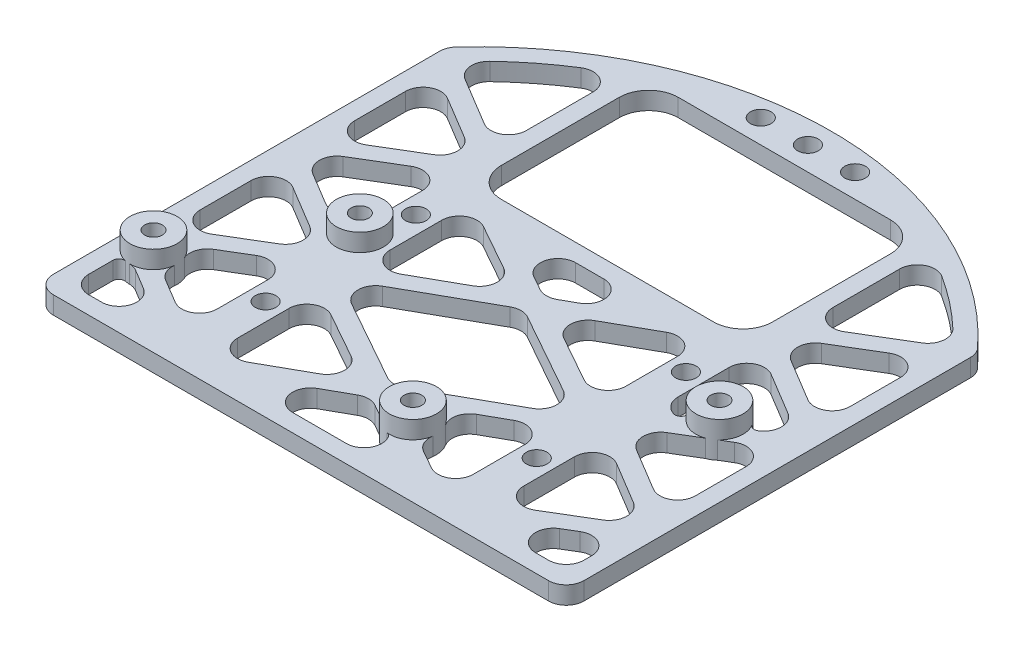
SolidWorks part; units mm, degrees
ref_plane "Front Plane" through (0, 0, 0) normal (0, 0, 1) x (1, 0, 0)
ref_plane "Top Plane" through (0, 0, 0) normal (0, 1, 0) x (1, 0, 0)
ref_plane "Right Plane" through (0, 0, 0) normal (1, 0, 0) x (0, 0, -1)
sketch "Sketch1" plane through (0, 0, 0) normal (0, 1, 0) x (1, 0, 0)
  line L0 (-45, -30) -> (45, -30)
  line L1 (45, -30) -> (45, 39.6863)
  line L2 (-45, -30) -> (-45, 39.6863)
  line L3 (0, 0) -> (0, 50000) construction
  arc A0 (-45, 39.6863) -> (45, 39.6863) centre (0, 0) cw
  dimension "D3" = 60
  dimension "D1" = 90
  dimension "D2" = 30
extrude "Boss-Extrude1" add sketch "Sketch1" along normal blind 3
sketch "Sketch2" plane through (0, 3, 0) normal (0, 1, 0) x (1, 0, 0)
  line L0 (0, 0) -> (0, 50000) construction
  line L1 (-45, -30) -> (45, -30) construction
  line L2 (-21.0323, 60) -> (49978.9677, 60) construction
  line L3 (-23, 52) -> (23, 52)
  line L4 (-23, 52) -> (-23, 22)
  line L5 (-23, 22) -> (23, 22)
  line L6 (23, 52) -> (23, 22)
  arc A0 (45, 39.6863) -> (-45, 39.6863) centre (0, 0) ccw construction
  point P4 (0, -30)
  dimension "D1" = 46
  dimension "D2" = 30
  dimension "D3" = 8
extrude "Cut-Extrude1" cut sketch "Sketch2" against normal through all
sketch "Sketch4" plane through (0, 3, 0) normal (0, 1, 0) x (1, 0, 0)
  circle A0 centre (23, -13) radius 1.75
  circle A1 centre (23, 12.2995) radius 1.75
  circle A2 centre (-23, 12.5) radius 1.75
  circle A3 centre (-23, -13) radius 1.75
  dimension "D1" = 3.5
extrude "Cut-Extrude3" cut sketch "Sketch4" against normal through all
sketch "Sketch8" plane through (0, 3, 0) normal (0, 1, 0) x (1, 0, 0)
  line L0 (0, 0) -> (0, 50000) construction
  line L1 (-4.2053, 56) -> (49995.7947, 56) construction
  circle A0 centre (0, 56) radius 1.75
  circle A1 centre (0, 56) radius 1.75 construction
  circle A2 centre (-8, 56) radius 1.75
  circle A3 centre (8, 56) radius 1.75
  dimension "D1" = 16
extrude "Cut-Extrude6" cut sketch "Sketch8" against normal through all
sketch "Sketch9" plane through (0, 3, 0) normal (0, 1, 0) x (1, 0, 0)
  line L0 (-42, 35.0364) -> (-42, 15.8207)
  line L1 (-42, 38.5357) -> (-26, 28.9279)
  line L2 (-42, -27) -> (-26, -27)
  line L3 (-42, 35.0364) -> (-26, 25.4286)
  line L4 (-13.8683, 19) -> (13.8683, 19)
  line L5 (-45, 39.6863) -> (-45, -30) construction
  line L6 (13.8683, 19) -> (0, 11.2199)
  line L7 (0, 11.2199) -> (-13.8683, 19)
  line L8 (-26, 25.4286) -> (-42, 15.8207)
  line L9 (-20, 19) -> (-3.0658, 9.5)
  line L10 (-3.0658, 9.5) -> (-20, 0)
  line L11 (20, 19) -> (3.0658, 9.5)
  line L12 (3.0658, 9.5) -> (20, 0)
  line L13 (-20, -3.4398) -> (0, 7.7801)
  line L14 (0, 7.7801) -> (20, -3.4398)
  line L15 (-20, -3.4398) -> (0, -14.6597)
  line L16 (0, -14.6597) -> (20, -3.4398)
  line L17 (20, -6.8797) -> (3.0658, -16.3797) construction
  line L18 (3.0658, -16.3797) -> (20, -25.8797) construction
  line L19 (20, -25.8797) -> (20, -6.8797)
  line L20 (0, 0) -> (0, -50000) construction
  line L21 (-20, -6.8797) -> (-20, -25.8797)
  line L22 (-20, 0) -> (-20, 19)
  line L23 (-26, 21.9292) -> (-42, 12.3214)
  line L24 (-42, 12.3214) -> (-26, 2.7136)
  line L25 (42, -27) -> (26, -27)
  line L26 (-42, 8.8221) -> (-26, -0.7857)
  line L27 (-26, -0.7857) -> (-42, -10.3935)
  line L28 (-26, -4.285) -> (-42, -13.8929)
  line L29 (-26, 50.7247) -> (-26, 28.9279)
  line L30 (-42, -13.8929) -> (-26, -23.5007)
  line L31 (-20, -25.8797) -> (-3.0658, -16.3797)
  line L32 (26, -23.5007) -> (26, -4.285)
  line L33 (42, 35.0364) -> (42, 15.8207)
  line L34 (-42, -17.3922) -> (-26, -27)
  line L35 (-39.5573, -13.8929) -> (49960.4427, -13.8929) construction
  line L36 (-28.2048, -0.7857) -> (-50028.2048, -0.7857) construction
  line L37 (-45, -30) -> (45, -30) construction
  line L38 (-39.4376, 12.3214) -> (49960.5624, 12.3214) construction
  line L39 (0, 0) -> (50000, 0) construction
  line L40 (-3.0658, -16.3797) -> (-20, -6.8797)
  line L41 (0, -18.0996) -> (-15.8654, -27)
  line L42 (-15.8654, -27) -> (15.8654, -27)
  line L43 (-23, 52) -> (-23, 22) construction
  line L44 (20, 19) -> (20, 0)
  line L45 (15.8654, -27) -> (0, -18.0996)
  line L46 (-28.496, 25.4286) -> (-50028.496, 25.4286) construction
  line L47 (-42, -17.3922) -> (-42, -27)
  line L48 (-26, -4.285) -> (-26, -23.5007)
  line L49 (-26, -23.5007) -> (-26, -27) construction
  line L50 (-26, 21.9292) -> (-26, 2.7136)
  line L51 (-42, 8.8221) -> (-42, -10.3935)
  line L52 (42, 38.5357) -> (26, 28.9279)
  line L53 (-42, -10.3935) -> (-42, -17.3922) construction
  line L54 (-42, 38.5357) -> (-42, 35.0364) construction
  line L55 (-26, 2.7136) -> (-26, -4.285) construction
  line L56 (42, 35.0364) -> (26, 25.4286)
  line L57 (26, 25.4286) -> (42, 15.8207)
  line L58 (26, 21.9292) -> (42, 12.3214)
  line L59 (42, 12.3214) -> (26, 2.7136)
  line L60 (42, 8.8221) -> (26, -0.7857)
  line L61 (26, -0.7857) -> (42, -10.3935)
  line L62 (26, -4.285) -> (42, -13.8929)
  line L63 (42, -13.8929) -> (26, -23.5007)
  line L64 (42, -17.3922) -> (26, -27)
  line L65 (26, 28.9279) -> (26, 50.7247)
  line L66 (26, 2.7136) -> (26, 21.9292)
  line L67 (42, 8.8221) -> (42, -10.3935)
  line L68 (42, -17.3922) -> (42, -27)
  line L69 (26, 28.9279) -> (26, 21.9292) construction
  line L70 (26, 2.7136) -> (26, -4.285) construction
  line L71 (42, -10.3935) -> (42, -17.3922) construction
  line L72 (42, 15.8207) -> (42, 8.8221) construction
  line L73 (-6.272, -3.4398) -> (49993.728, -3.4398) construction
  line L74 (-23, 22) -> (23, 22) construction
  line L75 (-20, 19) -> (-13.8683, 19) construction
  line L76 (13.8683, 19) -> (20, 19) construction
  line L77 (-20, 0) -> (-20, -6.8797) construction
  line L78 (20, 0) -> (20, -6.8797) construction
  line L79 (23, 22) -> (23, 52) construction
  line L80 (5, -15.2946) -> (5, -17.4647)
  line L81 (5, -17.4647) -> (20, -25.8797)
  line L82 (5, -15.2946) -> (20, -6.8797)
  arc A7 (-42, 38.5357) -> (-26, 50.7247) centre (0, 0) cw
  arc A8 (45, 39.6863) -> (-45, 39.6863) centre (0, 0) ccw construction
  arc A9 (42, 38.5357) -> (26, 50.7247) centre (0, 0) ccw
  dimension "D10" = 3
  dimension "D15" = 3
  dimension "D2" = 3
  dimension "D3" = 3
  dimension "D4" = 3
  dimension "D5" = 3
  dimension "D6" = 3
  dimension "D7" = 3
  dimension "D8" = 3
  dimension "D9" = 3
  dimension "D11" = 3
  dimension "D12" = 3
  dimension "D13" = 15
  dimension "D16" = 3
  dimension "D17" = 3
  dimension "D18" = 3
  dimension "D19" = 3
extrude "Cut-Extrude7" cut sketch "Sketch9" against normal through all
fillet "Fillet1" radius 5 4 edges at (-23, 1.5, -22) (23, 1.5, -22) (23, 1.5, -52) (-23, 1.5, -52)
sketch "Sketch5" plane through (0, 0, 0) normal (0, 1, 0) x (1, 0, 0)
  line L0 (-45, -30) -> (45, -30) construction
  line L1 (45, -30) -> (45, 39.6863) construction
  line L2 (-45, 39.6863) -> (-45, -30) construction
  circle A0 centre (-25, 5) radius 4
  circle A1 centre (-40, -15) radius 4
  circle A2 centre (7, -18) radius 4
  circle A3 centre (33, 8) radius 4
  dimension "D1" = 8
  dimension "D2" = 26
  dimension "D3" = 12
  dimension "D4" = 26
  dimension "D5" = 12
  dimension "D6" = 15
  dimension "D7" = 20
  dimension "D8" = 5
  dimension "D9" = 15
extrude "Boss-Extrude2" add sketch "Sketch5" along normal blind 6
sketch "Sketch6" plane through (0, 6, 0) normal (0, 1, 0) x (1, 0, 0)
  circle A0 centre (-25, 5) radius 1.5
  circle A1 centre (-40, -15) radius 1.5
  circle A2 centre (7, -18) radius 1.5
  circle A3 centre (33, 8) radius 1.5
  dimension "D1" = 3
extrude "Cut-Extrude4" cut sketch "Sketch6" against normal through all
fillet "Fillet2" radius 3 66 edges at (26, 1.5, 23.5007) (42, 1.5, 13.8929) (26, 1.5, 0.7857) (42, 1.5, 10.3935) (26, 1.5, -2.7136) (42, 1.5, -12.3214) (26, 1.5, -25.4286) (42, 1.5, -15.8207) (26, 1.5, 27) (42, 1.5, 27) (26, 1.5, -28.9279) (42, 1.5, -38.5357) (-26, 1.5, 23.5007) (-42, 1.5, 10.3935) (-26, 1.5, 0.7857) (-42, 1.5, -12.3214) (-42, 1.5, -15.8207) (-26, 1.5, -25.4286) (-26, 1.5, 27) (-42, 1.5, -38.5357) (-26, 1.5, -28.9279) (-42, 1.5, 27) (-26, 1.5, -21.9292) (26, 1.5, -21.9292) (26, 1.5, 4.285) (26, 1.5, -50.7247) (-42, 1.5, -8.8221) (-42, 1.5, -35.0364) (-26, 1.5, 4.285) (-45, 1.5, 30) (45, 1.5, 30) (42, 1.5, 17.3922) (42, 1.5, -8.8221) (42, 1.5, -35.0364) (-26, 1.5, -50.7247) (-39.3983, 1.5, 18.9545) (-26, 1.5, -8.873) (-28.9681, 1.5, -4.4959) (-36.6129, 1.5, 17.1278) (-38.0384, 1.5, 11.514) (45, 1.5, -39.6863) (-45, 1.5, -39.6863) (-13.8683, 1.5, -19) (15.8654, 1.5, 27) (-15.8654, 1.5, 27) (-20, 1.5, 0) (-20, 1.5, 25.8797) (-20, 1.5, 3.4398) (20, 1.5, 3.4398) (13.8683, 1.5, -19) (0, 1.5, 14.6597) (0, 1.5, -11.2199) (20, 1.5, 0) (3.6115, 1.5, 20.1256) (20, 1.5, -19) (0, 1.5, 18.0996) (-20, 1.5, 6.8797) (0, 1.5, -7.7801) (-20, 1.5, -19) (20, 1.5, 6.8797) (20, 1.5, 25.8797) (10.2095, 1.5, 20.3872) (7.289, 1.5, 14.0105) (3.0658, 1.5, -9.5) (-3.0658, 1.5, -9.5) (-3.0658, 1.5, 16.3797)
fillet "Fillet3" radius 1 4 edges at (36.8135, 1.5, -9.207) (30.1424, 1.5, -5.2011) (-42, 1.5, 18.4641) (6.9522, 1.5, 21.9997)
